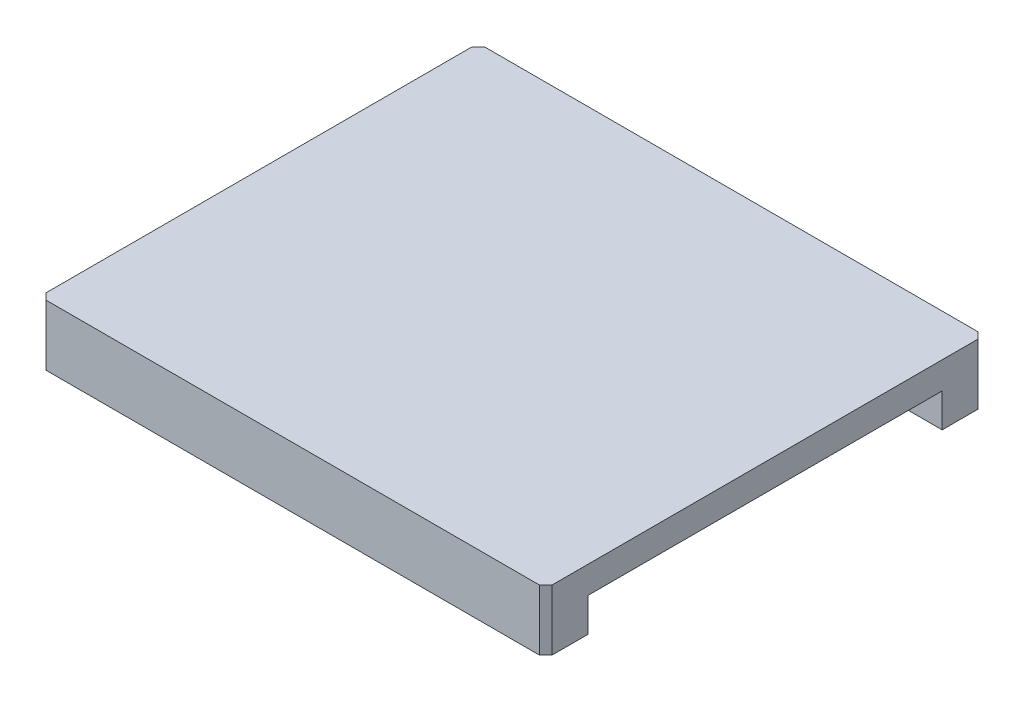
SolidWorks part; units mm, degrees
material "PLA"
ref_plane "Piano frontale" through (0, 0, 0) normal (0, 0, 1) x (1, 0, 0)
ref_plane "Piano superiore" through (0, 0, 0) normal (0, 1, 0) x (1, 0, 0)
ref_plane "Piano destro" through (0, 0, 0) normal (1, 0, 0) x (0, 0, -1)
sketch "Schizzo16" plane through (0, 0, 0) normal (1, 0, 0) x (0, 0, -1)
  line L0 (0, 0) -> (5, 0)
  line L1 (5, 0) -> (5, 4)
  line L2 (5, 4) -> (47, 4)
  line L3 (47, 4) -> (47, 0)
  line L4 (47, 0) -> (52, 0)
  line L5 (52, 0) -> (52, 7.2)
  line L6 (52, 7.2) -> (0, 7.2)
  line L7 (0, 7.2) -> (0, 0)
  point P3 (49.2896, 7.7832)
  dimension "D1" = 5
  dimension "D2" = 4
  dimension "D3" = 42
  dimension "D4" = 7.2
extrude "Estrusione-Estrusione9" add sketch "Schizzo16" along normal blind 60
chamfer "Smusso1" distance 0.75 angle 45 4 edges at (0, 3.6, 0) (0, 3.6, -52) (60, 3.6, -52) (60, 3.6, 0)
